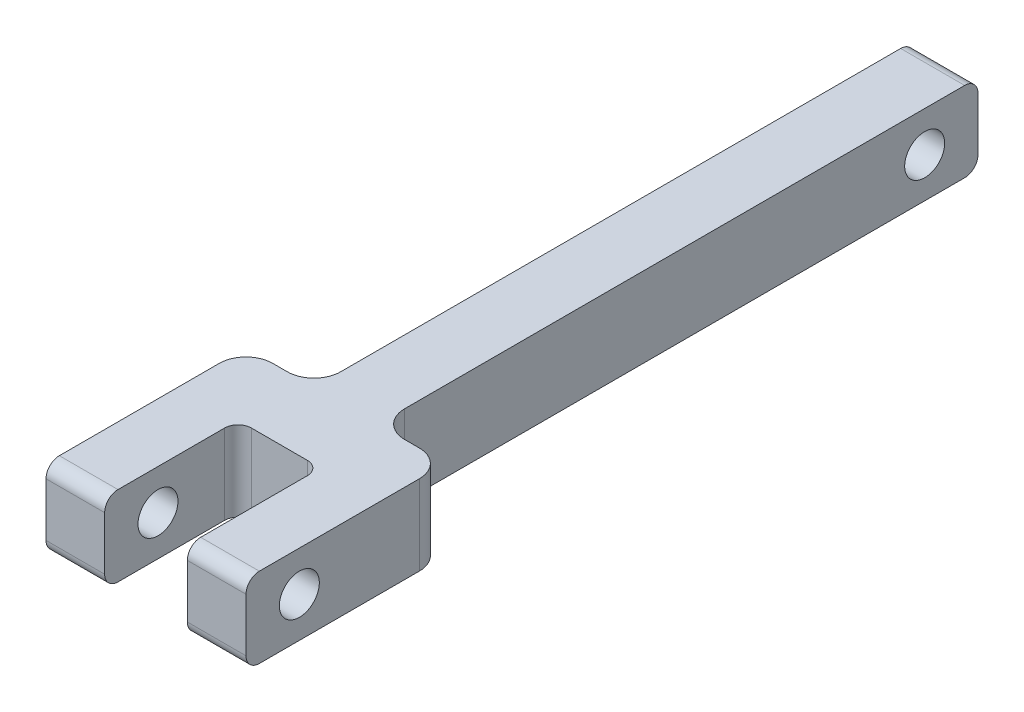
SolidWorks part; units mm, degrees
ref_plane "Alzado" through (0, 0, 0) normal (0, 0, 1) x (1, 0, 0)
ref_plane "Planta" through (0, 0, 0) normal (0, 1, 0) x (1, 0, 0)
ref_plane "Vista lateral" through (0, 0, 0) normal (1, 0, 0) x (0, 0, -1)
sketch "Croquis1" plane through (0, 0, 0) normal (1, 0, 0) x (0, 0, -1)
  line L0 (-29, 3) -> (29, 3)
  line L2 (-30, 0) -> (30, 0) construction
  line L3 (-30, 2) -> (-30, -2)
  line L4 (-29, -3) -> (29, -3)
  line L5 (30, 2) -> (30, -2)
  arc A0 (-30, -2) -> (-29, -3) centre (-29, -2) ccw
  arc A1 (-30, 2) -> (-29, 3) centre (-29, 2) cw
  arc A2 (29, -3) -> (30, -2) centre (29, -2) ccw
  arc A3 (29, 3) -> (30, 2) centre (29, 2) cw
  point P1 (0, 0)
  point P9 (-30, -3)
  point P13 (-30, 3)
  point P16 (30, -3)
  point P19 (30, 3)
  dimension "D3" = 1
  dimension "D4" = 1
  dimension "D1" = 3
  dimension "D2" = 60
extrude "Saliente-Extruir1" add sketch "Croquis1" along normal mid plane 4.8
sketch "Croquis2" plane through (0, 0, 0) normal (1, 0, 0) x (0, 0, -1)
  line L0 (-30, 2) -> (-30, -2) construction
  line L1 (30, -2) -> (30, 2) construction
  circle A0 centre (-26, 0) radius 1.5
  circle A1 centre (26, 0) radius 1.5
  dimension "D1" = 3
  dimension "D3" = 3
  dimension "D2" = 4
  dimension "D4" = 4
extrude "Cortar-Extruir1" cut sketch "Croquis2" against normal through all both and the other way through all
sketch "Croquis3" plane through (0, 0, 0) normal (1, 0, 0) x (0, 0, -1)
  line L0 (-30, 2) -> (-30, -2) construction
  line L1 (-30, 2) -> (-30, -2)
  line L2 (-29, 3) -> (-15, 3)
  line L3 (29, 3) -> (-29, 3) construction
  line L4 (-15, 3) -> (-15, -3)
  line L5 (-29, -3) -> (29, -3) construction
  line L6 (-15, -3) -> (-29, -3)
  circle A0 centre (-26, 0) radius 1.5 construction
  circle A1 centre (-26, 0) radius 1.5
  arc A2 (-29, 3) -> (-30, 2) centre (-29, 2) ccw construction
  arc A3 (-29, 3) -> (-30, 2) centre (-29, 2) ccw
  arc A4 (-30, -2) -> (-29, -3) centre (-29, -2) ccw construction
  arc A5 (-30, -2) -> (-29, -3) centre (-29, -2) ccw
  dimension "D1" = 15
extrude "Saliente-Extruir2" add sketch "Croquis3" along normal mid plane 15
sketch "Croquis4" plane through (0, 0, 0) normal (1, 0, 0) x (0, 0, -1)
  line L0 (-29, 3) -> (-20, 3)
  line L1 (-15, 3) -> (-29, 3) construction
  line L2 (-20, 3) -> (-20, -3)
  line L3 (-29, -3) -> (-15, -3) construction
  line L4 (-30, 2) -> (-30, -2)
  line L5 (-29, -3) -> (-15, -3)
  line L6 (-15, -3) -> (-15, 3)
  line L7 (-15, 3) -> (-29, 3)
  line L8 (-30, 2) -> (-30, -2)
  line L12 (-20, -3) -> (-29, -3)
  arc A2 (-29, 3) -> (-30, 2) centre (-29, 2) ccw
  arc A3 (-30, -2) -> (-29, -3) centre (-29, -2) ccw
  arc A4 (-29, 3) -> (-30, 2) centre (-29, 2) ccw
  arc A5 (-30, -2) -> (-29, -3) centre (-29, -2) ccw
  dimension "D2" = 10
  dimension "D1" = 0
extrude "Cortar-Extruir2" cut sketch "Croquis4" against normal mid plane 6.2
fillet "Redondeo1" radius 2 4 edges at (2.4, 0, 15) (-2.4, 0, 15) (7.5, 0, 15) (-7.5, 0, 15)
fillet "Redondeo2" radius 1 2 edges at (3.1, 0, 20) (-3.1, 0, 20)
